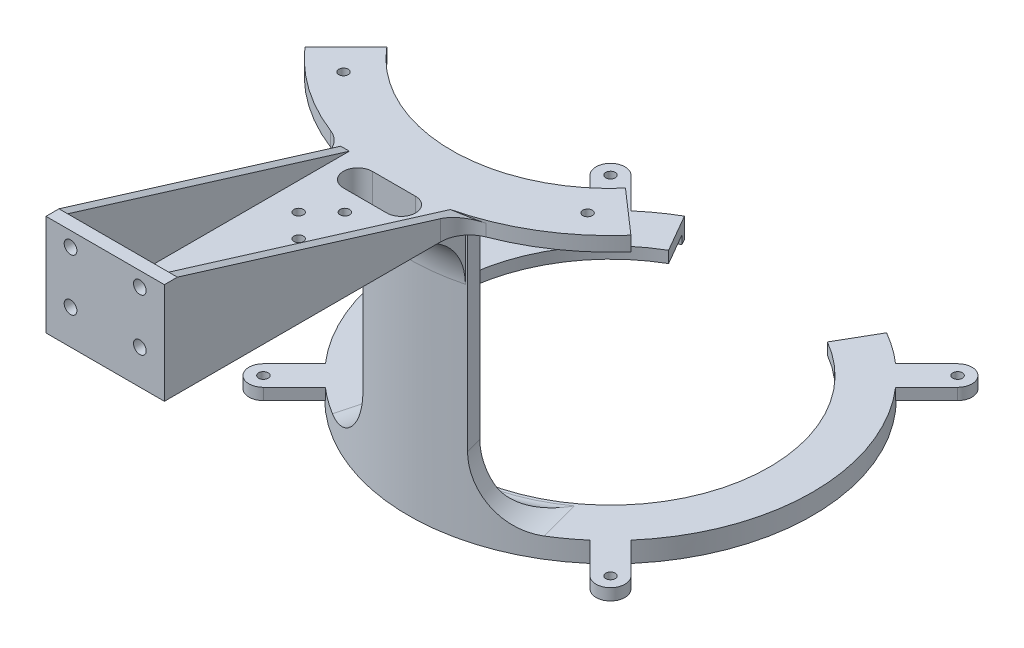
SolidWorks part; units mm, degrees
ref_plane "前视基准面" through (0, 0, 0) normal (0, 0, 1) x (1, 0, 0)
ref_plane "上视基准面" through (0, 0, 0) normal (0, 1, 0) x (1, 0, 0)
ref_plane "右视基准面" through (0, 0, 0) normal (1, 0, 0) x (0, 0, -1)
other "Configuration Table"
sketch "草图1" plane through (0, 0, 0) normal (0, 1, 0) x (1, 0, 0)
  line L0 (-1000, 0) -> (-7.0711, 0) construction
  line L1 (0, -1000) -> (0, -7.0711) construction
  line L3 (7.0711, 0) -> (49000, 0) construction
  line L4 (0, 0) -> (35355.3391, 35355.3391) construction
  line L5 (0, 0) -> (-35355.3391, 35355.3391) construction
  line L6 (-63.6396, -56.5685) -> (-52.9066, -45.8355)
  line L7 (-61.2708, -58.9374) -> (-58.9374, -61.2708)
  line L8 (58.9374, 61.2708) -> (61.2708, 58.9374)
  line L9 (-56.5685, -63.6396) -> (-45.8355, -52.9066)
  line L10 (-63.6396, -56.5685) -> (63.6396, 56.5685) construction
  line L11 (56.5685, 63.6396) -> (-56.5685, -63.6396) construction
  line L12 (56.5685, -63.6396) -> (45.8355, -52.9066)
  line L13 (58.9374, -61.2708) -> (61.2708, -58.9374)
  line L14 (-61.2708, 58.9374) -> (-58.9374, 61.2708)
  line L15 (63.6396, -56.5685) -> (52.9066, -45.8355)
  line L16 (56.5685, -63.6396) -> (-56.5685, 63.6396) construction
  line L17 (-63.6396, 56.5685) -> (63.6396, -56.5685) construction
  line L18 (-45.8355, 52.9066) -> (-56.5685, 63.6396)
  line L19 (-52.9066, 45.8355) -> (-63.6396, 56.5685)
  line L20 (27.5, 47.6314) -> (35, 60.6218)
  line L21 (45.8355, 52.9066) -> (56.5685, 63.6396)
  line L22 (52.9066, 45.8355) -> (63.6396, 56.5685)
  line L23 (-27.5, 47.6314) -> (-35, 60.6218)
  arc A0 (-27.5, 47.6314) -> (27.5, 47.6314) centre (0, 0) ccw
  arc A1 (-52.9066, 45.8355) -> (-52.9066, -45.8355) centre (0, 0) ccw
  arc A2 (-56.5685, 63.6396) -> (-63.6396, 56.5685) centre (-60.1041, 60.1041) ccw
  arc A3 (63.6396, 56.5685) -> (56.5685, 63.6396) centre (60.1041, 60.1041) ccw
  arc A4 (-56.5685, -63.6396) -> (-63.6396, -56.5685) centre (-60.1041, -60.1041) cw
  circle A5 centre (-60.1041, 60.1041) radius 1.65
  arc A6 (63.6396, -56.5685) -> (56.5685, -63.6396) centre (60.1041, -60.1041) cw
  circle A7 centre (60.1041, 60.1041) radius 1.65
  circle A8 centre (60.1041, -60.1041) radius 1.65
  circle A9 centre (-60.1041, -60.1041) radius 1.65
  arc A10 (-35, 60.6218) -> (-45.8355, 52.9066) centre (0, 0) ccw
  arc A11 (45.8355, 52.9066) -> (35, 60.6218) centre (0, 0) ccw
  arc A12 (-45.8355, -52.9066) -> (45.8355, -52.9066) centre (0, 0) ccw
  arc A13 (52.9066, -45.8355) -> (52.9066, 45.8355) centre (0, 0) ccw
  dimension "D1" = 140
  dimension "D2" = 110
  dimension "D12" = 3.3
  dimension "D5" = 45
  dimension "D6" = 170
  dimension "D7" = 170
  dimension "D8" = 10
  dimension "D9" = 10
  dimension "D10" = 0
  dimension "D11" = 0
  dimension "D13" = 4
extrude "凸台-拉伸1" add sketch "草图1" along normal blind 4 contours L15 A13 L22 A3 L21 A11 L20 A0 L23 A10 L18 A2 L19 A1 L6 A4 L9 A12 L12 A6 A5 A7 A8 A9
sketch "草图2" plane through (0, 0, 0) normal (0, -1, 0) x (1, 0, 0)
  line L10 (52.9066, 45.8355) -> (63.6396, 56.5685)
  line L11 (56.5685, 63.6396) -> (45.8355, 52.9066)
  line L12 (-45.8355, 52.9066) -> (-56.5685, 63.6396)
  line L13 (-63.6396, 56.5685) -> (-52.9066, 45.8355)
  line L14 (-52.9066, -45.8355) -> (-63.6396, -56.5685)
  line L15 (-56.5685, -63.6396) -> (-45.8355, -52.9066)
  line L16 (-35, -60.6218) -> (-27.5, -47.6314)
  line L17 (27.5, -47.6314) -> (35, -60.6218)
  line L18 (45.8355, -52.9066) -> (56.5685, -63.6396)
  line L19 (63.6396, -56.5685) -> (52.9066, -45.8355)
  line L20 (52.9066, 45.8355) -> (63.6396, 56.5685)
  line L21 (56.5685, 63.6396) -> (45.8355, 52.9066)
  line L22 (-45.8355, 52.9066) -> (-56.5685, 63.6396)
  line L23 (-63.6396, 56.5685) -> (-52.9066, 45.8355)
  line L24 (-52.9066, -45.8355) -> (-63.6396, -56.5685)
  line L25 (-56.5685, -63.6396) -> (-45.8355, -52.9066)
  line L26 (-35, -60.6218) -> (-27.5, -47.6314)
  line L27 (27.5, -47.6314) -> (35, -60.6218)
  line L28 (45.8355, -52.9066) -> (56.5685, -63.6396)
  line L29 (63.6396, -56.5685) -> (52.9066, -45.8355)
  arc A0 (33.875, -58.6732) -> (-33.875, -58.6732) centre (0, 0) ccw
  circle A1 centre (0, 0) radius 70
  arc A10 (63.6396, 56.5685) -> (56.5685, 63.6396) centre (60.1041, 60.1041) ccw
  arc A11 (45.8355, 52.9066) -> (-45.8355, 52.9066) centre (0, 0) ccw
  arc A12 (-56.5685, 63.6396) -> (-63.6396, 56.5685) centre (-60.1041, 60.1041) ccw
  arc A13 (-52.9066, 45.8355) -> (-52.9066, -45.8355) centre (0, 0) ccw
  arc A14 (-63.6396, -56.5685) -> (-56.5685, -63.6396) centre (-60.1041, -60.1041) ccw
  arc A15 (-45.8355, -52.9066) -> (-35, -60.6218) centre (0, 0) ccw
  arc A16 (27.5, -47.6314) -> (-27.5, -47.6314) centre (0, 0) ccw
  arc A17 (35, -60.6218) -> (45.8355, -52.9066) centre (0, 0) ccw
  arc A18 (56.5685, -63.6396) -> (63.6396, -56.5685) centre (60.1041, -60.1041) ccw
  arc A19 (52.9066, -45.8355) -> (52.9066, 45.8355) centre (0, 0) ccw
  arc A20 (63.6396, 56.5685) -> (56.5685, 63.6396) centre (60.1041, 60.1041) ccw
  arc A21 (45.8355, 52.9066) -> (-45.8355, 52.9066) centre (0, 0) ccw
  arc A22 (-56.5685, 63.6396) -> (-63.6396, 56.5685) centre (-60.1041, 60.1041) ccw
  arc A23 (-52.9066, 45.8355) -> (-52.9066, -45.8355) centre (0, 0) ccw
  arc A24 (-63.6396, -56.5685) -> (-56.5685, -63.6396) centre (-60.1041, -60.1041) ccw
  arc A25 (-45.8355, -52.9066) -> (-35, -60.6218) centre (0, 0) ccw
  arc A26 (27.5, -47.6314) -> (-27.5, -47.6314) centre (0, 0) ccw
  arc A27 (35, -60.6218) -> (45.8355, -52.9066) centre (0, 0) ccw
  arc A28 (56.5685, -63.6396) -> (63.6396, -56.5685) centre (60.1041, -60.1041) ccw
  arc A29 (52.9066, -45.8355) -> (52.9066, 45.8355) centre (0, 0) ccw
  arc M28 (45.8355, 52.9066) -> (-45.8355, 52.9066) centre (0, 0) ccw
  arc M32 (-52.9066, 45.8355) -> (-52.9066, -45.8355) centre (0, 0) ccw
  arc M36 (-45.8355, -52.9066) -> (-35, -60.6218) centre (0, 0) ccw
  line M37 (-35, -60.6218) -> (-27.5, -47.6314)
  arc M40 (35, -60.6218) -> (45.8355, -52.9066) centre (0, 0) ccw
  arc M44 (52.9066, -45.8355) -> (52.9066, 45.8355) centre (0, 0) ccw
  dimension "D2" = 135.5
  dimension "D1" = 0
extrude "凸台-拉伸2" add sketch "草图2" along normal blind 3 contours A1 A0 L27 M40 M44 M28 M32 M36 M37
sketch "草图3" plane through (0, 4, 0) normal (0, 1, 0) x (1, 0, 0)
  line L0 (-45.8355, -52.9066) -> (-36.0136, -41.5695)
  line L1 (45.8355, -52.9066) -> (36.0136, -41.5695)
  line L2 (0, 0) -> (-18.1173, -67.6148)
  line L3 (0, 0) -> (18.1173, -67.6148)
  line L4 (0, -1000) -> (0, 49000) construction
  line L10 (63.6396, -56.5685) -> (52.9066, -45.8355)
  line L11 (52.9066, 45.8355) -> (63.6396, 56.5685)
  line L12 (56.5685, 63.6396) -> (45.8355, 52.9066)
  line L13 (35, 60.6218) -> (27.5, 47.6314)
  line L14 (-27.5, 47.6314) -> (-35, 60.6218)
  line L15 (-45.8355, 52.9066) -> (-56.5685, 63.6396)
  line L16 (-63.6396, 56.5685) -> (-52.9066, 45.8355)
  line L17 (-52.9066, -45.8355) -> (-63.6396, -56.5685)
  line L18 (-56.5685, -63.6396) -> (-45.8355, -52.9066)
  line L19 (45.8355, -52.9066) -> (56.5685, -63.6396)
  line L20 (63.6396, -56.5685) -> (52.9066, -45.8355)
  line L21 (52.9066, 45.8355) -> (63.6396, 56.5685)
  line L22 (56.5685, 63.6396) -> (45.8355, 52.9066)
  line L23 (35, 60.6218) -> (27.5, 47.6314)
  line L24 (-27.5, 47.6314) -> (-35, 60.6218)
  line L25 (-45.8355, 52.9066) -> (-56.5685, 63.6396)
  line L26 (-63.6396, 56.5685) -> (-52.9066, 45.8355)
  line L27 (-52.9066, -45.8355) -> (-63.6396, -56.5685)
  line L28 (-56.5685, -63.6396) -> (-45.8355, -52.9066)
  line L29 (45.8355, -52.9066) -> (56.5685, -63.6396)
  circle A0 centre (0, 0) radius 64
  arc A10 (52.9066, -45.8355) -> (52.9066, 45.8355) centre (0, 0) ccw
  arc A11 (63.6396, 56.5685) -> (56.5685, 63.6396) centre (60.1041, 60.1041) ccw
  arc A12 (45.8355, 52.9066) -> (35, 60.6218) centre (0, 0) ccw
  arc A13 (-27.5, 47.6314) -> (27.5, 47.6314) centre (0, 0) ccw
  arc A14 (-35, 60.6218) -> (-45.8355, 52.9066) centre (0, 0) ccw
  arc A15 (-56.5685, 63.6396) -> (-63.6396, 56.5685) centre (-60.1041, 60.1041) ccw
  arc A16 (-52.9066, 45.8355) -> (-52.9066, -45.8355) centre (0, 0) ccw
  arc A17 (-63.6396, -56.5685) -> (-56.5685, -63.6396) centre (-60.1041, -60.1041) ccw
  arc A18 (-45.8355, -52.9066) -> (45.8355, -52.9066) centre (0, 0) ccw
  arc A19 (56.5685, -63.6396) -> (63.6396, -56.5685) centre (60.1041, -60.1041) ccw
  arc A20 (52.9066, -45.8355) -> (52.9066, 45.8355) centre (0, 0) ccw
  arc A21 (63.6396, 56.5685) -> (56.5685, 63.6396) centre (60.1041, 60.1041) ccw
  arc A22 (45.8355, 52.9066) -> (35, 60.6218) centre (0, 0) ccw
  arc A23 (-27.5, 47.6314) -> (27.5, 47.6314) centre (0, 0) ccw
  arc A24 (-35, 60.6218) -> (-45.8355, 52.9066) centre (0, 0) ccw
  arc A25 (-56.5685, 63.6396) -> (-63.6396, 56.5685) centre (-60.1041, 60.1041) ccw
  arc A26 (-52.9066, 45.8355) -> (-52.9066, -45.8355) centre (0, 0) ccw
  arc A27 (-63.6396, -56.5685) -> (-56.5685, -63.6396) centre (-60.1041, -60.1041) ccw
  arc A28 (-45.8355, -52.9066) -> (45.8355, -52.9066) centre (0, 0) ccw
  arc A29 (56.5685, -63.6396) -> (63.6396, -56.5685) centre (60.1041, -60.1041) ccw
  arc M42 (-45.8355, -52.9066) -> (45.8355, -52.9066) centre (0, 0) ccw
  dimension "D2" = 128
  dimension "D3" = 15
  dimension "D4" = 15
  dimension "D1" = 0
extrude "凸台-拉伸4" add sketch "草图3" along normal blind 90 contours L4 A28 L3 A0 | L4 A0 L2 M42
fillet "圆角1" radius 20 1 edges at (-17.3409, 4, 64.717)
fillet "圆角2" radius 20 1 edges at (17.3409, 4, 64.717)
fillet "圆角3" radius 8 2 edges at (0, 4, 64) (20.7513, 11.516, 60.5424)
sketch "草图4" plane through (0, 94, 0) normal (0, 1, 0) x (1, 0, 0)
  line L0 (0, 0) -> (17.5, 0)
  line L1 (-17.5, -65.3109) -> (-17.5, -175)
  line L2 (17.5, -65.3109) -> (17.5, -175)
  line L3 (-17.5, -175) -> (17.5, -175)
  line L4 (0, -1134) -> (0, -55) construction
  line L5 (-1000, -159) -> (49000, -159) construction
  line L6 (0, 0) -> (0, 48866) construction
  line L7 (16.5644, -61.8193) -> (18.1173, -67.6148) construction
  line L8 (-16.5644, -61.8193) -> (-18.1173, -67.6148) construction
  line L9 (16.5644, -61.8193) -> (17.5, -65.3109)
  line L10 (-16.5644, -61.8193) -> (-17.5, -65.3109)
  circle A2 centre (0, -159) radius 5.25
  circle A3 centre (0, -159) radius 8
  circle A4 centre (0, -151) radius 1.65
  circle A5 centre (8, -159) radius 1.65
  circle A6 centre (0, -167) radius 1.65
  circle A7 centre (-8, -159) radius 1.65
  arc A8 (-16.5644, -61.8193) -> (16.5644, -61.8193) centre (0, 0) ccw construction
  arc A9 (-16.5644, -61.8193) -> (16.5644, -61.8193) centre (0, 0) ccw
  arc M9 (16.5644, -61.8193) -> (-16.5644, -61.8193) centre (0, 0) cw
  line M10 (-16.5644, -61.8193) -> (-18.1173, -67.6148)
  arc M11 (-18.1173, -67.6148) -> (18.1173, -67.6148) centre (0, 0) ccw
  line M12 (18.1173, -67.6148) -> (16.5644, -61.8193)
  dimension "D4" = 10.5
  dimension "D7" = 16
  dimension "D8" = 3.3
  dimension "D2" = 175
  dimension "D3" = 17.5
  dimension "D5" = 16
  dimension "D6" = 17.5
  dimension "D9" = 4
extrude "凸台-拉伸6" add sketch "草图4" along normal blind 5 contours L1 L3 L2 A7 A3 A4 A5 A6 M11 | L2 L1 M12 M9 M10 M11 | A7 A3 A6 A5 A4 A2
fillet "圆角4" radius 20 1 edges at (0, 94, 70)
sketch "草图5" plane through (0, 99, 0) normal (0, 1, 0) x (1, 0, 0)
  line L0 (-17.5, -170.5) -> (17.5, -170.5)
  line L5 (-17.5, -65.3109) -> (-17.5, -175)
  line L6 (-17.5, -175) -> (17.5, -175)
  line L7 (17.5, -175) -> (17.5, -65.3109)
  line L8 (17.5, -65.3109) -> (16.5644, -61.8193)
  line L9 (-16.5644, -61.8193) -> (-17.5, -65.3109)
  line L10 (-17.5, -65.3109) -> (-17.5, -175)
  line L11 (-17.5, -175) -> (17.5, -175)
  line L12 (17.5, -175) -> (17.5, -65.3109)
  line L13 (17.5, -65.3109) -> (16.5644, -61.8193)
  line L14 (-16.5644, -61.8193) -> (-17.5, -65.3109)
  arc A1 (-16.5644, -61.8193) -> (16.5644, -61.8193) centre (0, 0) ccw
  arc A2 (-16.5644, -61.8193) -> (16.5644, -61.8193) centre (0, 0) ccw
  line M12 (-17.5, -65.3109) -> (-17.5, -175)
  line M13 (-17.5, -175) -> (17.5, -175)
  line M14 (17.5, -175) -> (17.5, -65.3109)
  dimension "D2" = 4.5
  dimension "D1" = 0
extrude "凸台-拉伸7" add sketch "草图5" along normal blind 30 contours L0 M12 M13 M14
sketch "草图6" plane through (0, 99, 0) normal (0, 1, 0) x (1, 0, 0)
  line L0 (17.5, -65.3109) -> (17.5, -170.5) construction
  arc A0 (-27.5, 47.6314) -> (27.5, 47.6314) centre (0, 0) ccw construction
  arc A1 (-27.5, 47.6314) -> (27.5, 47.6314) centre (0, 0) ccw
  circle A2 centre (0, -100) radius 8
  circle A4 centre (0, -92) radius 1.65
  circle A5 centre (8, -100) radius 1.65
  circle A6 centre (0, -108) radius 1.65
  circle A7 centre (-8, -100) radius 1.65
  dimension "D2" = 16
  dimension "D4" = 3.3
  dimension "D1" = 100
  dimension "D3" = 17.5
  dimension "D5" = 4
extrude "切除-拉伸2" cut sketch "草图6" against normal blind 13 contours A2 A7 | A2 A7 | A2 A4 | A2 A4 | A2 A5 | A2 A5 | A2 A6 | A2 A6
sketch "草图7" plane through (0, 99, 0) normal (0, 1, 0) x (1, 0, 0)
  line L0 (-42.2654, -35.1943) -> (-56.4506, -49.3795)
  line L1 (-63.6396, -56.5685) -> (-52.9066, -45.8355) construction
  line L2 (56.4506, -49.3795) -> (41.3971, -36.2116)
  line L3 (63.6396, -56.5685) -> (52.9066, -45.8355) construction
  line L4 (-63.6396, -56.5685) -> (-52.9066, -45.8355)
  line L5 (-17.5, -170.5) -> (17.5, -170.5) construction
  line L6 (17.5, -65.3109) -> (17.5, -170.5) construction
  line L7 (-17.5, -65.3109) -> (-17.5, -170.5) construction
  line L8 (-17.5, -170.5) -> (17.5, -170.5)
  line L9 (17.5, -72.9298) -> (17.5, -170.5)
  line L10 (-17.5, -72.9298) -> (-17.5, -170.5)
  line L11 (0, -1000) -> (0, 49000) construction
  arc A0 (-27.5, 47.6314) -> (27.5, 47.6314) centre (0, 0) ccw construction
  arc A1 (-42.2654, -35.1943) -> (41.3971, -36.2116) centre (0, 0) ccw
  arc A2 (-56.4506, -49.3795) -> (-17.5, -72.9298) centre (0, 0) ccw
  arc A3 (17.5, -72.9298) -> (56.4506, -49.3795) centre (0, 0) ccw
  circle A4 centre (-42.2654, -50.1943) radius 1.65
  arc A6 (-45.8355, -52.9066) -> (-36.6806, -59.6199) centre (0, 0) ccw construction
  circle A7 centre (42.2654, -50.1943) radius 1.65
  line M20 (-17.5, -65.3109) -> (-17.5, -170.5)
  line M22 (17.5, -170.5) -> (17.5, -65.3109)
  line M23 (17.5, -65.3109) -> (16.5644, -61.8193)
  arc M24 (16.5644, -61.8193) -> (-16.5644, -61.8193) centre (0, 0) cw
  line M25 (-16.5644, -61.8193) -> (-17.5, -65.3109)
  dimension "D1" = 150
  dimension "D4" = 65.6188
  dimension "D5" = 3.3
  dimension "D2" = 180
  dimension "D3" = 15
extrude "凸台-拉伸8" add sketch "草图7" against normal blind 5 contours L11 A1 L0 A2 A4 M24 M20 M25 | L11 A3 L2 A1 A7 M24 M23 M22
sketch "草图8" plane through (0, 0, 175) normal (0, 0, 1) x (1, 0, 0)
  line L1 (-12, 124) -> (12, 124)
  line L2 (-12, 124) -> (-12, 106)
  line L3 (-12, 106) -> (12, 106)
  line L4 (-17.5, 94) -> (17.5, 94)
  line L5 (17.5, 94) -> (17.5, 129)
  line L6 (17.5, 129) -> (-17.5, 129)
  line L7 (-17.5, 129) -> (-17.5, 94)
  line L8 (-17.5, 94) -> (17.5, 94)
  line L9 (17.5, 94) -> (17.5, 129)
  line L10 (17.5, 129) -> (-17.5, 129)
  line L11 (-17.5, 129) -> (-17.5, 94)
  line L12 (12, 124) -> (12, 106)
  line L13 (-12, 124) -> (12, 106) construction
  line L14 (-12, 106) -> (12, 124) construction
  circle A0 centre (-12, 124) radius 2.2
  circle A1 centre (12, 124) radius 2.2
  circle A2 centre (12, 106) radius 2.2
  circle A3 centre (-12, 106) radius 2.2
  point P2 (0, 115)
  dimension "D6" = 4.4
  dimension "D7" = 4.4
  dimension "D8" = 4.4
  dimension "D9" = 4.4
  dimension "D2" = 18
  dimension "D3" = 24
  dimension "D4" = 5
  dimension "D5" = 5.5
  dimension "D1" = 0
extrude "切除-拉伸3" cut sketch "草图8" against normal blind 5 contours L1 A0 L2 | L2 A3 L3 | L3 A2 L12 | L2 A0 L1 | L12 A2 L3 | L3 A3 L2 | L12 A1 L1 | L1 A1 L12
sketch "草图9" plane through (-17.5, 0, 0) normal (-1, 0, 0) x (0, 0, 1)
  line L0 (72.9298, 94) -> (88.2822, 94)
  line L1 (72.9298, 99) -> (170.5, 129)
  line L8 (72.9298, 99) -> (72.9298, 94)
  line L9 (72.9298, 94) -> (67.7772, 94)
  line L10 (67.7772, 94) -> (67.7772, 74)
  line L11 (88.2822, 94) -> (175, 94)
  line L12 (175, 94) -> (175, 129)
  line L13 (175, 129) -> (170.5, 129)
  line L14 (170.5, 129) -> (170.5, 99)
  line L15 (170.5, 99) -> (72.9298, 99)
  line L16 (72.9298, 99) -> (72.9298, 94)
  line L19 (88.2822, 94) -> (175, 94)
  line L20 (175, 94) -> (175, 129)
  line L21 (175, 129) -> (170.5, 129)
  spline S1 degree 3 poles (550.0371, 950.0268) (591.5552, -117.6993) (50.8952, -5.2422) (68.4555, 79.2566) (68.8567, 80.5156) (69.6412, 82.3318) (69.9334, 82.9251) (70.5803, 84.087) (70.9362, 84.6568) (72.0734, 86.2904) (72.9299, 87.2926) (74.3583, 88.6693) (74.8597, 89.1077) (75.9077, 89.9371) (76.4476, 90.323) (78.1135, 91.3975) (79.2851, 92.0037) (81.1349, 92.7465) (81.7693, 92.9666) (83.0433, 93.3411) (83.6857, 93.4969) (136.7789, 103.7503) (223.3489, -86.5394) (408.1024, -853.4774) knots -7.813558 -7.813558 -7.813558 -7.813558 0.125 0.125 0.25 0.25 0.3125 0.3125 0.375 0.375 0.5 0.5 0.5625 0.5625 0.625 0.625 0.75 0.75 0.8125 0.8125 0.875 0.875 5.936627 5.936627 5.936627 5.936627 only from (67.7772, 74) to (88.2822, 94)
  line M11 (72.9298, 99) -> (72.9298, 94)
  line M15 (88.2822, 94) -> (175, 94)
  line M16 (175, 94) -> (175, 129)
  line M17 (175, 129) -> (170.5, 129)
  line M18 (170.5, 129) -> (170.5, 99)
  line M19 (170.5, 99) -> (72.9298, 99)
  dimension "D2" = 0
  dimension "D1" = 0
extrude "凸台-拉伸9" add sketch "草图9" along normal blind 3 contours L1 M19 M18 | L0 M11 M15 M16 M17 M18 M19
fillet "圆角5" radius 10 3 edges at (-17.5, 96.5, 72.9298) (-19, 94, 72.9298) (-20.5, 96.5, 72.9298)
sketch "草图10" plane through (17.5, 0, 0) normal (1, 0, 0) x (0, 0, -1)
  line L0 (-170.5, 129) -> (-72.9298, 99)
  line L2 (-72.9298, 94) -> (-88.2822, 94)
  line L8 (-67.7772, 94) -> (-72.9298, 94)
  line L9 (-72.9298, 94) -> (-72.9298, 99)
  line L10 (-72.9298, 99) -> (-170.5, 99)
  line L11 (-170.5, 99) -> (-170.5, 129)
  line L12 (-170.5, 129) -> (-175, 129)
  line L13 (-175, 129) -> (-175, 94)
  line L14 (-175, 94) -> (-88.2822, 94)
  line L15 (-67.7772, 74) -> (-67.7772, 94)
  line L16 (-67.7772, 94) -> (-72.9298, 94)
  line L17 (-72.9298, 94) -> (-72.9298, 99)
  line L20 (-170.5, 129) -> (-175, 129)
  line L21 (-175, 129) -> (-175, 94)
  line L22 (-175, 94) -> (-88.2822, 94)
  spline S1 degree 3 poles (-408.1022, -853.4766) (-223.3489, -86.5393) (-136.7789, 103.7503) (-83.6857, 93.4969) (-83.0433, 93.3411) (-81.7693, 92.9666) (-81.1349, 92.7465) (-79.2851, 92.0037) (-78.1135, 91.3975) (-76.4476, 90.323) (-75.9077, 89.9371) (-74.8597, 89.1077) (-74.3583, 88.6693) (-72.9299, 87.2926) (-72.0734, 86.2904) (-70.9362, 84.6568) (-70.5803, 84.087) (-69.9334, 82.9251) (-69.6412, 82.3318) (-68.8567, 80.5156) (-68.4555, 79.2566) (-50.8952, -5.2421) (-591.5542, -117.6991) (-550.0372, 950.0239) knots -4.936625 -4.936625 -4.936625 -4.936625 0.125 0.125 0.1875 0.1875 0.25 0.25 0.375 0.375 0.4375 0.4375 0.5 0.5 0.625 0.625 0.6875 0.6875 0.75 0.75 0.875 0.875 8.813551 8.813551 8.813551 8.813551 only from (-88.2822, 94) to (-67.7772, 74)
  line M11 (-72.9298, 94) -> (-72.9298, 99)
  line M12 (-72.9298, 99) -> (-170.5, 99)
  line M13 (-170.5, 99) -> (-170.5, 129)
  line M14 (-170.5, 129) -> (-175, 129)
  line M15 (-175, 129) -> (-175, 94)
  line M16 (-175, 94) -> (-88.2822, 94)
  dimension "D2" = 0
  dimension "D1" = 0
extrude "凸台-拉伸10" add sketch "草图10" along normal blind 3 contours L0 M13 M12 | L2 M11 M12 M13 M14 M15 M16
fillet "圆角6" radius 10 4 edges at (17.5, 96.5, 72.9298) (19, 99, 72.9298) (19, 94, 72.9298) (20.5, 96.5, 72.9298)
sketch "草图11" plane through (0, 99, 0) normal (0, 1, 0) x (1, 0, 0)
  line L0 (-7.5, -80) -> (7.5, -80) construction
  line L1 (-7.5, -75) -> (7.5, -75)
  line L2 (-7.5, -85) -> (7.5, -85)
  line L3 (17.5, -72.9298) -> (17.5, -170.5) construction
  arc A0 (-7.5, -75) -> (-7.5, -85) centre (-7.5, -80) ccw
  arc A1 (7.5, -85) -> (7.5, -75) centre (7.5, -80) ccw
  point P2 (0, -80)
  dimension "D1" = 80
  dimension "D2" = 10
  dimension "D3" = 15
  dimension "D4" = 17.5
extrude "切除-拉伸5" cut sketch "草图11" against normal through all both and the other way through all
